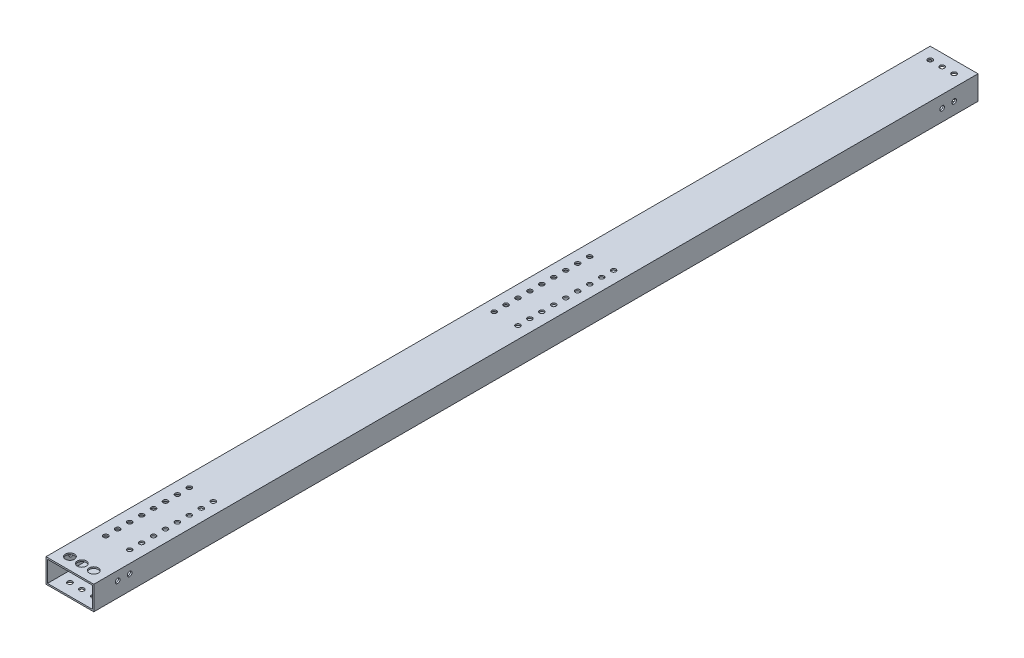
SolidWorks part; units mm, degrees
material "6061-T6 (SS)"
ref_plane "Front Plane" through (0, 0, 0) normal (0, 0, 1) x (1, 0, 0)
ref_plane "Top Plane" through (0, 0, 0) normal (0, 1, 0) x (1, 0, 0)
ref_plane "Right Plane" through (0, 0, 0) normal (1, 0, 0) x (0, 0, -1)
sketch "Sketch1" plane through (0, 0, 0) normal (0, 0, 1) x (1, 0, 0)
  line L0 (-23.8125, 11.1125) -> (23.8125, 11.1125)
  line L1 (-25.4, -12.7) -> (25.4, -12.7)
  line L2 (-25.4, -12.7) -> (-25.4, 12.7)
  line L3 (-25.4, 12.7) -> (25.4, 12.7)
  line L4 (25.4, -12.7) -> (25.4, 12.7)
  line L5 (-25.4, -12.7) -> (25.4, 12.7) construction
  line L6 (-25.4, 12.7) -> (25.4, -12.7) construction
  line L7 (23.8125, -11.1125) -> (23.8125, 11.1125)
  line L8 (-23.8125, -11.1125) -> (23.8125, -11.1125)
  line L9 (-23.8125, -11.1125) -> (-23.8125, 11.1125)
  point P0 (0, 0)
  dimension "D1" = 50.8
  dimension "D2" = 25.4
  dimension "D3" = 1.5875
extrude "Boss-Extrude1" add sketch "Sketch1" along normal mid plane 939.8
sketch "Sketch4" plane through (0, 12.7, 0) normal (0, 1, 0) x (1, 0, 0)
  line L0 (25.4, -469.9) -> (-25.4, -469.9) construction
  circle A0 centre (-12.7, -457.2) radius 4.826
  circle A1 centre (0, -457.2) radius 4.826
  circle A2 centre (12.7, -457.2) radius 4.826
  dimension "D1" = 9.652
  dimension "D2" = 12.7
  dimension "D3" = 12.7
  dimension "D4" = 12.7
extrude "Cut-Extrude3" cut sketch "Sketch4" against normal up to surface (1.5875 mm away) contours A0 | A1 | A2 region at (-12.7, 12.7, 457.2) region at (0, 12.7, 457.2) region at (12.7, 12.7, 457.2) up to face at (0, 11.1125, 0)
sketch "Sketch5" plane through (0, -12.7, 0) normal (0, -1, 0) x (1, 0, 0)
  circle A0 centre (-12.7, 457.2) radius 4.826 construction
  circle A1 centre (0, 457.2) radius 4.826 construction
  circle A2 centre (12.7, 457.2) radius 4.826 construction
  circle A3 centre (-12.7, 457.2) radius 4.826
  circle A4 centre (0, 457.2) radius 4.826
  circle A5 centre (12.7, 457.2) radius 4.826
  circle A6 centre (-12.7, 457.2) radius 2.5527
  circle A7 centre (0, 457.2) radius 2.5527
  circle A8 centre (12.7, 457.2) radius 2.5527
  dimension "D1" = 5.1054
extrude "Cut-Extrude4" cut sketch "Sketch5" against normal up to surface (1.5875 mm away) contours A8 | A7 | A6 region at (-12.7, -12.7, 457.2) region at (0, -12.7, 457.2) region at (12.7, -12.7, 457.2) up to face at (0, -11.1125, 0)
sketch "Sketch6" plane through (0, -12.7, 0) normal (0, -1, 0) x (1, 0, 0)
  line L0 (-25.4, -469.9) -> (25.4, -469.9) construction
  circle A0 centre (-12.7, -457.2) radius 2.5527
  circle A1 centre (0, -457.2) radius 2.5527
  circle A2 centre (12.7, -457.2) radius 2.5527
  dimension "D1" = 5.1054
  dimension "D2" = 12.7
  dimension "D3" = 12.7
  dimension "D4" = 12.7
extrude "Cut-Extrude5" cut sketch "Sketch6" against normal through all contours A2 | A1 | A0 region at (-12.7, -12.7, -457.2) region at (0, -12.7, -457.2) region at (12.7, -12.7, -457.2)
sketch "Sketch7" plane through (25.4, 0, 0) normal (1, 0, 0) x (0, 0, -1)
  line L0 (-469.9, -12.7) -> (-469.9, 12.7) construction
  line L2 (469.9, -12.7) -> (469.9, 12.7) construction
  line L3 (-469.9, -12.7) -> (469.9, -12.7) construction
  circle A0 centre (-457.2, 3.175) radius 2.4892
  circle A1 centre (-444.5, 3.175) radius 2.4892
  circle A2 centre (-431.8, 3.175) radius 2.4892
  circle A3 centre (-419.1, 3.175) radius 2.4892
  circle A4 centre (457.2, 0) radius 2.4892
  circle A5 centre (444.5, 0) radius 2.4892
  circle A6 centre (431.8, 0) radius 2.4892
  dimension "D1" = 4.9784
  dimension "D7" = 4.9784
  dimension "D8" = 12.7
  dimension "D2" = 12.7
  dimension "D3" = 12.7
  dimension "D4" = 12.7
  dimension "D5" = 12.7
  dimension "D6" = 15.875
  dimension "D9" = 12.7
  dimension "D10" = 12.7
  dimension "D11" = 12.7
extrude "Cut-Extrude6" cut sketch "Sketch7" against normal through all contours A6 | A5 | A1 | A2 region at (25.4, 3.175, 444.5) region at (25.4, 3.175, 431.8) region at (25.4, 0, -444.5) region at (25.4, 0, -431.8)
sketch "Sketch10" plane through (0, 12.7, 0) normal (0, 1, 0) x (1, 0, 0)
  line L1 (25.4, -469.9) -> (-25.4, -469.9) construction
  line L3 (-25.4, -469.9) -> (-25.4, 469.9) construction
  circle A0 centre (-12.7, -419.1) radius 2.4892
  circle A5 centre (12.7, -419.1) radius 2.4892
  circle A6 centre (-12.7, -406.4) radius 2.4892
  circle A7 centre (12.7, -406.4) radius 2.4892
  circle A8 centre (-12.7, -393.7) radius 2.4892
  circle A9 centre (12.7, -393.7) radius 2.4892
  circle A10 centre (-12.7, -381) radius 2.4892
  circle A11 centre (12.7, -381) radius 2.4892
  circle A12 centre (-12.7, -368.3) radius 2.4892
  circle A13 centre (12.7, -368.3) radius 2.4892
  circle A14 centre (-12.7, -355.6) radius 2.4892
  circle A15 centre (12.7, -355.6) radius 2.4892
  circle A16 centre (-12.7, -342.9) radius 2.4892
  circle A17 centre (12.7, -342.9) radius 2.4892
  circle A18 centre (-12.7, -330.2) radius 2.4892
  circle A19 centre (12.7, -330.2) radius 2.4892
  circle A20 centre (-12.7, -6.35) radius 2.4892
  circle A21 centre (12.7, -6.35) radius 2.4892
  circle A22 centre (-12.7, 6.35) radius 2.4892
  circle A23 centre (12.7, 6.35) radius 2.4892
  circle A24 centre (-12.7, 19.05) radius 2.4892
  circle A25 centre (12.7, 19.05) radius 2.4892
  circle A26 centre (-12.7, 31.75) radius 2.4892
  circle A27 centre (12.7, 31.75) radius 2.4892
  circle A28 centre (-12.7, 44.45) radius 2.4892
  circle A29 centre (12.7, 44.45) radius 2.4892
  circle A30 centre (-12.7, 57.15) radius 2.4892
  circle A31 centre (12.7, 57.15) radius 2.4892
  circle A32 centre (-12.7, 69.85) radius 2.4892
  circle A33 centre (12.7, 69.85) radius 2.4892
  circle A34 centre (-12.7, 82.55) radius 2.4892
  circle A35 centre (12.7, 82.55) radius 2.4892
  circle A36 centre (-12.7, 95.25) radius 2.4892
  circle A37 centre (12.7, 95.25) radius 2.4892
  dimension "D1" = 25.4
  dimension "D3" = 4.9784
  dimension "D2" = 12.7
  dimension "D4" = 50.8
  dimension "D5" = 12.7
  dimension "D6" = 323.85
  dimension "D8" = 12.7
  dimension "D9" = 9
extrude "Cut-Extrude8" cut sketch "Sketch10" against normal up to next (1.5875 mm away)
